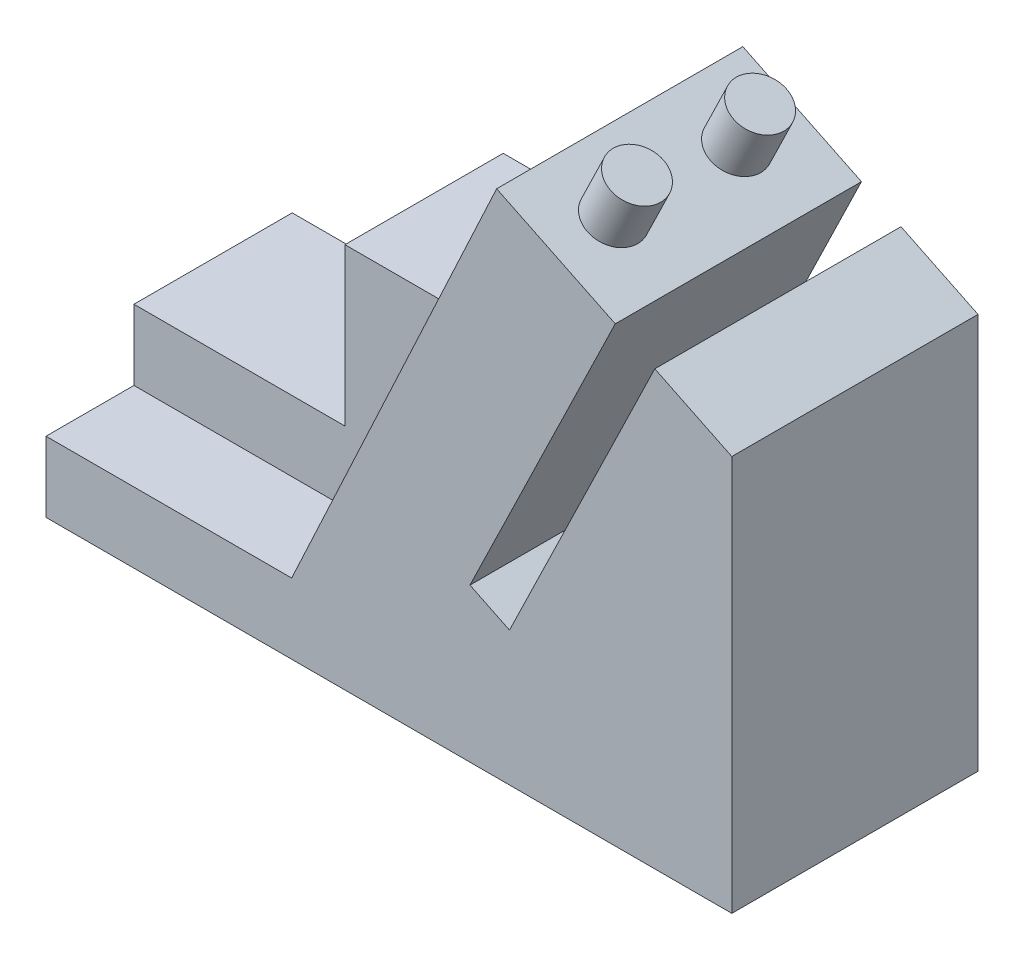
SolidWorks part; units mm, degrees
material "Ductile Iron"
ref_plane "Front Plane" through (0, 0, 0) normal (0, 0, 1) x (1, 0, 0)
ref_plane "Top Plane" through (0, 0, 0) normal (0, 1, 0) x (1, 0, 0)
ref_plane "Right Plane" through (0, 0, 0) normal (1, 0, 0) x (0, 0, -1)
sketch "Sketch7" plane through (0, 0, 0) normal (0, 0, 1) x (1, 0, 0)
  line L0 (577.5941, 669.1194) -> (499.5941, 669.1194)
  line L1 (499.5941, 669.1194) -> (499.5941, 677.1194)
  line L4 (550.8483, 727.1194) -> (564.3391, 720.5621)
  line L5 (577.5941, 714.1194) -> (577.5941, 669.1194)
  line L6 (499.5941, 677.1194) -> (527.533, 677.1194)
  line L8 (499.5941, 677.1194) -> (499.5941, 685.1194)
  line L9 (499.5941, 685.1194) -> (523.5941, 685.1194)
  line L10 (523.5941, 685.1194) -> (523.5941, 702.9846)
  line L12 (527.533, 677.1194) -> (550.8483, 727.1194)
  line L13 (564.3391, 720.5621) -> (547.8131, 686.5621)
  line L14 (547.8131, 686.5621) -> (552.3101, 684.3763)
  line L15 (552.3101, 684.3763) -> (568.8361, 718.3763)
  line L16 (568.8361, 718.3763) -> (577.5941, 714.1194)
  line L17 (499.5941, 677.1194) -> (499.5941, 685.1194)
  line L18 (523.5941, 702.9846) -> (539.5941, 702.9846)
  dimension "D1" = 78
  dimension "D2" = 45
  dimension "D3" = 8
  dimension "D4" = 65
  dimension "D5" = 58
  dimension "D6" = 16
  dimension "D7" = 16
  dimension "D8" = 24
  dimension "D10" = 15
  dimension "D11" = 5
  dimension "D12" = 34
extrude "Boss-Extrude7" add sketch "Sketch7" along normal blind 28 contours L16 L15 L14 L13 L4 L12 L6 L1 L0 L5 region at (538.5941, 670.0914, 0)
extrude "Boss-Extrude8" add sketch "Sketch7<7>" along normal blind 18 contours L18 L10 L9 L8 L6 L12 region at (500.0704, 681.1194, 0)
sketch "Sketch7<7>" plane through (0, 0, 0) normal (0, 0, 1) x (1, 0, 0) same geometry as "Sketch7"
sketch "Sketch9" plane through (391.1514, 804.7414, 0) normal (0.4372, 0.8994, 0) x (0.8994, -0.4372, 0)
  line L0 (184.6111, -7) -> (184.6111, -21) construction
  line L1 (-31.9, 0) -> (31.9, 0) construction
  circle A0 centre (184.6111, -21) radius 3
  circle A1 centre (184.6111, -7) radius 3
  dimension "D1" = 6
  dimension "D2" = 6
  dimension "D3" = 14
  dimension "D4" = 7
extrude "Boss-Extrude9" add sketch "Sketch9" along normal blind 6
